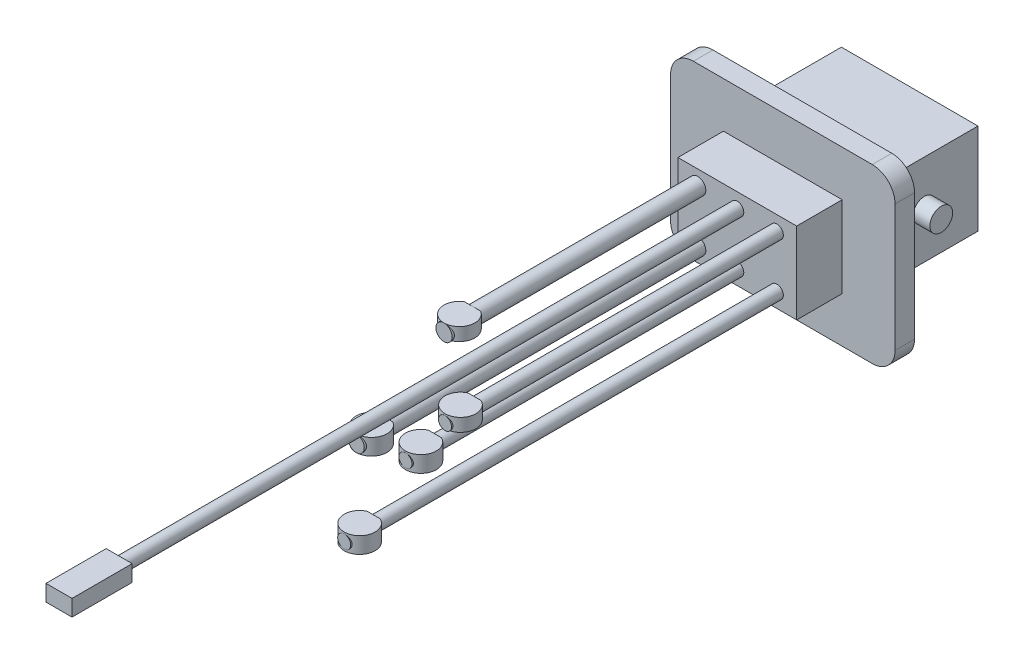
SolidWorks part; units mm, degrees
ref_plane "Front Plane" through (0, 0, 0) normal (0, 0, 1) x (1, 0, 0)
ref_plane "Top Plane" through (0, 0, 0) normal (0, 1, 0) x (1, 0, 0)
ref_plane "Right Plane" through (0, 0, 0) normal (1, 0, 0) x (0, 0, -1)
sketch "Sketch1" plane through (0, 0, 0) normal (0, 0, 1) x (1, 0, 0)
  line L1 (0, 0) -> (42, 0)
  line L2 (0, 0) -> (0, 28)
  line L3 (0, 28) -> (42, 28)
  line L4 (42, 0) -> (42, 28)
  dimension "D1" = 42
  dimension "D2" = 28
extrude "Boss-Extrude1" add sketch "Sketch1" along normal blind 33
sketch "Sketch2" plane through (0, 0, 33) normal (0, 0, 1) x (1, 0, 0)
  line L0 (0, 28) -> (42, 0) construction
  line L2 (-13.5, 40.5) -> (55.5, 40.5)
  line L3 (-13.5, 40.5) -> (-13.5, -12.5)
  line L4 (-13.5, -12.5) -> (55.5, -12.5)
  line L5 (55.5, 40.5) -> (55.5, -12.5)
  line L6 (-13.5, 40.5) -> (55.5, -12.5) construction
  line L7 (-13.5, -12.5) -> (55.5, 40.5) construction
  point P4 (21, 14)
  dimension "D1" = 69
  dimension "D2" = 53
extrude "Boss-Extrude2" add sketch "Sketch2" along normal blind 6
sketch "Sketch3" plane through (0, 0, 39) normal (0, 0, 1) x (1, 0, 0)
  line L0 (-13.5, 40.5) -> (55.5, -12.5) construction
  line L2 (2.75, 26.5) -> (39.25, 26.5)
  line L3 (2.75, 26.5) -> (2.75, 1.5)
  line L4 (2.75, 1.5) -> (39.25, 1.5)
  line L5 (39.25, 26.5) -> (39.25, 1.5)
  line L6 (2.75, 26.5) -> (39.25, 1.5) construction
  line L7 (2.75, 1.5) -> (39.25, 26.5) construction
  point P4 (21, 14)
  dimension "D1" = 36.5
  dimension "D2" = 25
extrude "Boss-Extrude3" add sketch "Sketch3" along normal blind 14
sketch "Sketch4" plane through (0, 0, 53) normal (0, 0, 1) x (1, 0, 0)
  line L0 (2.75, 10.5) -> (39.25, 10.5) construction
  line L1 (2.75, 26.5) -> (2.75, 1.5) construction
  line L2 (39.25, 1.5) -> (39.25, 26.5) construction
  line L3 (27.08, 10.5) -> (27.08, 1.5) construction
  line L4 (2.75, 1.5) -> (39.25, 1.5) construction
  line L5 (14.9167, 10.5) -> (14.9167, 1.5) construction
  line L6 (39.25, 1.5) -> (39.25, 26.5) construction
  line L7 (2.75, 10.5) -> (14.9167, 1.5) construction
  line L8 (14.9167, 1.5) -> (27.08, 10.5) construction
  line L9 (27.08, 10.5) -> (39.25, 1.5) construction
  line L12 (2.75, 14) -> (39.25, 14) construction
  line L13 (27.08, 17.5) -> (39.25, 26.5) construction
  line L14 (14.9167, 26.5) -> (27.08, 17.5) construction
  line L15 (2.75, 17.5) -> (14.9167, 26.5) construction
  line L16 (14.9167, 17.5) -> (14.9167, 26.5) construction
  line L17 (27.08, 17.5) -> (27.08, 26.5) construction
  line L18 (2.75, 17.5) -> (39.25, 17.5) construction
  circle A0 centre (8.8333, 6) radius 2.5
  circle A1 centre (20.9983, 6) radius 2
  circle A2 centre (33.165, 6) radius 2
  circle A3 centre (33.165, 22) radius 2
  circle A4 centre (20.9983, 22) radius 2
  circle A5 centre (8.8333, 22) radius 2.5
  dimension "D1" = 5
  dimension "D2" = 4
  dimension "D3" = 4
  dimension "D4" = 9
  dimension "D5" = 12.17
  dimension "D6" = 12.1667
extrude "Boss-Extrude4" add sketch "Sketch4" along normal blind 1
sketch "Sketch5" plane through (0, 0, 54) normal (0, 0, 1) x (1, 0, 0)
  circle A1 centre (8.8333, 22) radius 2.5
  circle A2 centre (8.8333, 22) radius 2.5
  dimension "D1" = 0
extrude "Boss-Extrude5" add sketch "Sketch5" along normal blind 77
sketch "Sketch6" plane through (0, 0, 54) normal (0, 0, 1) x (1, 0, 0)
  circle A1 centre (20.9983, 22) radius 2
  circle A2 centre (20.9983, 22) radius 2
  dimension "D1" = 0
extrude "Boss-Extrude6" add sketch "Sketch6" along normal blind 189
sketch "Sketch7" plane through (0, 0, 54) normal (0, 0, 1) x (1, 0, 0)
  circle A1 centre (33.165, 22) radius 2
  circle A2 centre (33.165, 22) radius 2
  dimension "D1" = 0
extrude "Boss-Extrude7" add sketch "Sketch7" along normal blind 101
ref_plane "Plane1" through (0, 24.5, 0) normal (0, 1, 0) x (0, 0, -1)
sketch "Sketch8" plane through (0, 24.5, 0) normal (0, 1, 0) x (0, 0, -1)
  line L0 (-53, -6.3333) -> (-131, -6.3333) construction
  line L1 (-131, -11.3333) -> (-53, -11.3333) construction
  line L2 (-131, -6.3333) -> (-131, -11.3333) construction
  line L3 (-122.2111, -6.3333) -> (-122.2111, -11.3333)
  line L4 (-53, -31.165) -> (-155, -31.165) construction
  line L5 (-155, -35.165) -> (-53, -35.165) construction
  line L6 (-155, -31.165) -> (-155, -35.165) construction
  line L7 (-145.9416, -31.165) -> (-145.9416, -35.165)
  arc A0 (-122.2111, -6.3333) -> (-122.2111, -11.3333) centre (-126.25, -8.8333) ccw
  arc A1 (-145.9416, -31.165) -> (-145.9416, -35.165) centre (-150.25, -33.165) ccw
  dimension "D1" = 4.75
  dimension "D2" = 4.75
extrude "Boss-Extrude8" add sketch "Sketch8" against normal blind 4
sketch "Sketch9" plane through (0, 0, 54) normal (0, 0, 1) x (1, 0, 0)
  circle A1 centre (8.8333, 6) radius 2.5
  circle A2 centre (8.8333, 6) radius 2.5
  dimension "D1" = 0
extrude "Boss-Extrude9" add sketch "Sketch9" along normal blind 104
sketch "Sketch10" plane through (0, 0, 54) normal (0, 0, 1) x (1, 0, 0)
  circle A1 centre (20.9983, 6) radius 2
  circle A2 centre (20.9983, 6) radius 2
  dimension "D1" = 0
extrude "Boss-Extrude10" add sketch "Sketch10" along normal blind 101
sketch "Sketch11" plane through (0, 0, 54) normal (0, 0, 1) x (1, 0, 0)
  circle A1 centre (33.165, 6) radius 2
  circle A2 centre (33.165, 6) radius 2
  dimension "D1" = 0
extrude "Boss-Extrude11" add sketch "Sketch11" along normal blind 132
ref_plane "Plane2" through (0, 8.5, 0) normal (0, 1, 0) x (0, 0, -1)
sketch "Sketch13" plane through (0, 8.5, 0) normal (0, 1, 0) x (0, 0, -1)
  line L0 (-158, -11.3333) -> (-53, -11.3333) construction
  line L1 (-158, -6.3333) -> (-158, -11.3333) construction
  line L2 (-149.2111, -6.3333) -> (-149.2111, -11.3333)
  line L3 (-53, -31.165) -> (-186, -31.165) construction
  line L4 (-186, -35.165) -> (-53, -35.165) construction
  line L6 (-186, -31.165) -> (-186, -35.165) construction
  line L7 (-176.9416, -31.165) -> (-176.9416, -35.165)
  line L8 (-53, -18.9983) -> (-155, -18.9983) construction
  line L9 (-155, -22.9983) -> (-53, -22.9983) construction
  line L10 (-155, -18.9983) -> (-155, -22.9983) construction
  line L11 (-145.9416, -18.9983) -> (-145.9416, -22.9983)
  arc A0 (-149.2111, -6.3333) -> (-149.2111, -11.3333) centre (-153.25, -8.8333) ccw
  arc A1 (-176.9416, -31.165) -> (-176.9416, -35.165) centre (-181.25, -33.165) ccw
  arc A2 (-145.9416, -18.9983) -> (-145.9416, -22.9983) centre (-150.25, -20.9983) ccw
  dimension "D1" = 4.75
  dimension "D3" = 4.75
  dimension "D4" = 4.75
  dimension "D2" = 5
extrude "Boss-Extrude12" add sketch "Sketch13" against normal blind 5
sketch "Sketch14" plane through (0, 0, 243) normal (0, 0, 1) x (1, 0, 0)
  line L1 (16.9983, 24.5) -> (24.9983, 24.5)
  line L2 (16.9983, 24.5) -> (16.9983, 19.5)
  line L3 (16.9983, 19.5) -> (24.9983, 19.5)
  line L4 (24.9983, 24.5) -> (24.9983, 19.5)
  line L5 (16.9983, 24.5) -> (24.9983, 19.5) construction
  line L6 (16.9983, 19.5) -> (24.9983, 24.5) construction
  point P0 (20.9983, 22)
  dimension "D1" = 5
  dimension "D2" = 8
extrude "Boss-Extrude13" add sketch "Sketch14" along normal blind 18.5
fillet "Fillet1" radius 7 4 edges at (-13.5, -12.5, 36) (-13.5, 40.5, 36) (55.5, -12.5, 36) (55.5, 40.5, 36)
sketch "Sketch15" plane through (0, 0, 0) normal (-1, 0, 0) x (0, 0, 1)
  line L0 (0, 28) -> (33, 0) construction
  circle A0 centre (16.5, 14) radius 3.5
  dimension "D1" = 7
extrude "Boss-Extrude14" add sketch "Sketch15" along normal blind 5.2
ref_plane "Plane3" through (21, 0, 0) normal (-1, 0, 0) x (0, 0, 1)
mirror "Mirror1" about plane through (21, 0, 0) normal (-1, 0, 0) of "Boss-Extrude14"
